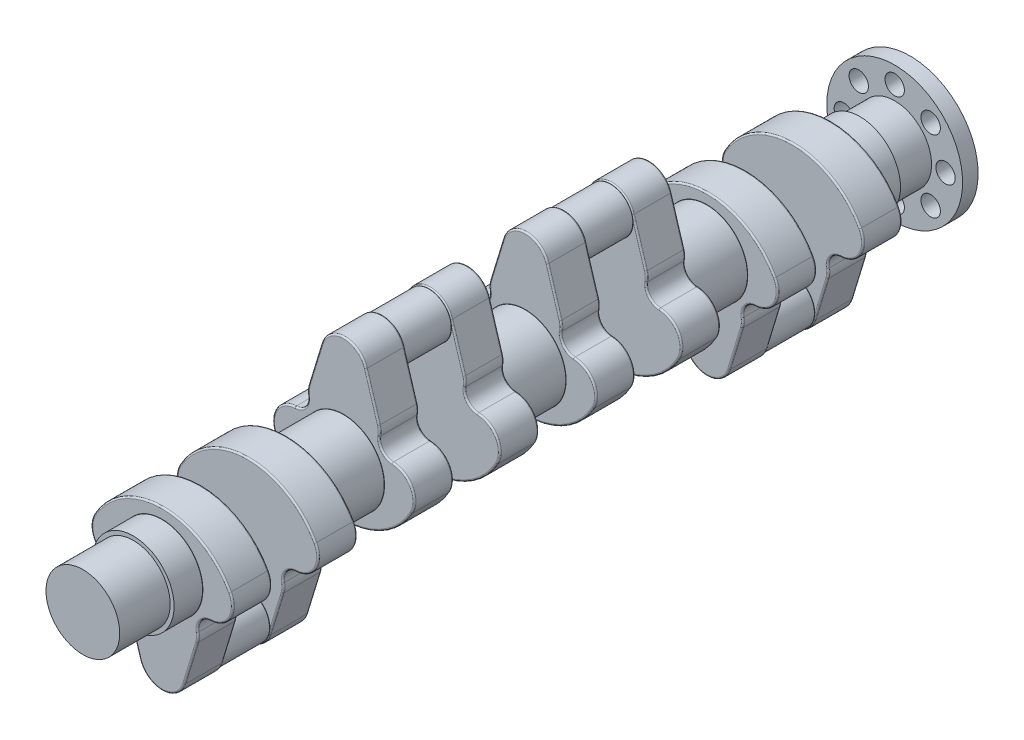
SolidWorks part; units mm, degrees
ref_plane "Front Plane" through (0, 0, 0) normal (0, 0, 1) x (1, 0, 0)
ref_plane "Top Plane" through (0, 0, 0) normal (0, 1, 0) x (1, 0, 0)
ref_plane "Right Plane" through (0, 0, 0) normal (1, 0, 0) x (0, 0, -1)
sketch "Sketch1" plane through (0, 0, 0) normal (0, 0, 1) x (1, 0, 0)
  line L0 (0, 91.3491) -> (0, -63.7647) construction
  line L1 (-19.0598, -8.6289) -> (-11.4785, -33.499)
  line L2 (19.0598, -8.6289) -> (11.4785, -33.499)
  arc A1 (-35.008, 19.3504) -> (-25.0013, 1.5555) centre (-24.5056, 13.5453) ccw
  arc A2 (-25.0013, 1.5555) -> (-19.0598, -8.6289) centre (-25.2905, -5.4385) cw
  arc A3 (-11.4785, -33.499) -> (0, -42) centre (0, -30) ccw
  arc A4 (11.4785, -33.499) -> (0, -42) centre (0, -30) cw
  arc A5 (25.0013, 1.5555) -> (19.0598, -8.6289) centre (25.2905, -5.4385) ccw
  arc A6 (35.008, 19.3504) -> (25.0013, 1.5555) centre (24.5056, 13.5453) cw
  arc A8 (-35.008, 19.3504) -> (0, 40) centre (0, 0) cw
  arc A9 (35.008, 19.3504) -> (0, 40) centre (0, 0) ccw
  point P14 (0, 0)
  point P22 (0, 0)
  point P23 (0, 0)
  point P24 (-19.0598, -8.6289)
  dimension "D1" = 40
  dimension "D2" = 12
  dimension "D3" = 7
  dimension "D5" = 12
  dimension "D4" = 26
  dimension "D6" = 82
extrude "Boss-Extrude1" add sketch "Sketch1" along normal blind 20
sketch "Sketch3" plane through (0, 0, 0) normal (0, 0, -1) x (-1, 0, 0)
  line L0 (0, 25.5673) -> (0, -22.9598) construction
  line L1 (-36.5056, 13.5453) -> (36.5056, 13.5453) construction
  arc A0 (-35.008, 19.3504) -> (-25.0013, 1.5555) centre (-24.5056, 13.5453) ccw construction
  arc A1 (25.0013, 1.5555) -> (35.008, 19.3504) centre (24.5056, 13.5453) ccw construction
  circle A2 centre (0, 13.5453) radius 21
  dimension "D1" = 42
extrude "Boss-Extrude2" add sketch "Sketch3" along normal blind 14.8
sketch "Sketch4" plane through (0, 0, 20) normal (0, 0, 1) x (1, 0, 0)
  circle A0 centre (0, -30) radius 11.5
  dimension "D1" = 23
extrude "Boss-Extrude3" add sketch "Sketch4" along normal blind 12
fillet "Fillet1" radius 10 2 edges at (19.0598, -8.6289, 10) (-19.0598, -8.6289, 10)
fillet "Fillet2" radius 0.8 20 edges at (19.8018, -1.094, 0) (18.5836, -9.1824, 0) (14.8208, -22.5349, 0) (0, -42, 0) (-14.8208, -22.5349, 0) (-18.5836, -9.1824, 0) (-19.8018, -1.094, 0) (-34.9653, 7.6634, 0) (0, 40, 0) (0, -42, 20) (-14.8208, -22.5349, 20) (-18.5836, -9.1824, 20) (-19.8018, -1.094, 20) (-34.9653, 7.6634, 20) (0, 40, 20) (34.9653, 7.6634, 20) (19.8018, -1.094, 20) (18.5836, -9.1824, 20) (34.9653, 7.6634, 0) (14.8208, -22.5349, 20)
fillet "Fillet3" radius 0.1 5 edges at (0, -18.5, 20) (-21, 13.5453, 0) (11.3113, -32.075, 20) (0, -41.5, 20) (-11.3113, -32.075, 20)
mirror "Mirror1" about plane through (0, -30, 32) normal (0, 0, 1) of bodies 103
pattern_linear "LPattern1" count 4 spacing 93.6 along (0, 0, -1) of bodies 104
sketch "Sketch5" plane through (0, 0, -295.6) normal (0, 0, -1) x (-1, 0, 0)
  point P0 (0, 13.5453)
  point P1 (0, 0)
sketch "Sketch6" plane through (0, 0, 78.8) normal (0, 0, 1) x (1, 0, 0)
  point P0 (0, 13.5453)
  point P1 (0, 0)
ref_axis "Axis1" through (0, 13.5453, -295.6) along (0, 0, 1)
move or copy body "Body-Move/Copy1" bodies to move or copy 106 105 copy no rotation origin (0, 13.5453, 0) rotation axis (0, 0, 1) rotation angle 180
combine bodies "Combine1" operation type add bodies to combine 107 108 109 104
sketch "Sketch7" plane through (0, 0, 78.8) normal (0, 0, 1) x (1, 0, 0)
  circle A0 centre (0, 13.5453) radius 19
  dimension "D1" = 38
extrude "Boss-Extrude4" add sketch "Sketch7" along normal blind 26
sketch "Sketch8" plane through (0, 0, -295.6) normal (0, 0, -1) x (-1, 0, 0)
  circle A0 centre (0, 13.5453) radius 19
  dimension "D1" = 38
extrude "Boss-Extrude5" add sketch "Sketch8" along normal blind 18
sketch "Sketch9" plane through (0, 0, -313.6) normal (0, 0, -1) x (-1, 0, 0)
  circle A0 centre (0, 13.5453) radius 35
  dimension "D1" = 70
extrude "Boss-Extrude6" add sketch "Sketch9" along normal blind 8
sketch "Sketch10" plane through (0, 0, -321.6) normal (0, 0, -1) x (-1, 0, 0)
  circle A0 centre (0, 39.763) radius 5
  circle A1 centre (18.5387, 32.084) radius 5
  circle A2 centre (26.2177, 13.5453) radius 5
  circle A3 centre (18.5387, -4.9935) radius 5
  circle A4 centre (0, -12.6725) radius 5
  circle A5 centre (-18.5387, -4.9935) radius 5
  circle A6 centre (-26.2177, 13.5453) radius 5
  circle A7 centre (-18.5387, 32.084) radius 5
  point P18 (0, 13.5453)
  dimension "D1" = 10
  dimension "D2" = 8
extrude "Cut-Extrude1" cut sketch "Sketch10" against normal blind 8
sketch "Sketch11" plane through (0, 0, -321.6) normal (0, 0, -1) x (-1, 0, 0)
  circle A0 centre (0, 13.5453) radius 15
  dimension "D1" = 30
extrude "Cut-Extrude2" cut sketch "Sketch11" against normal blind 2
